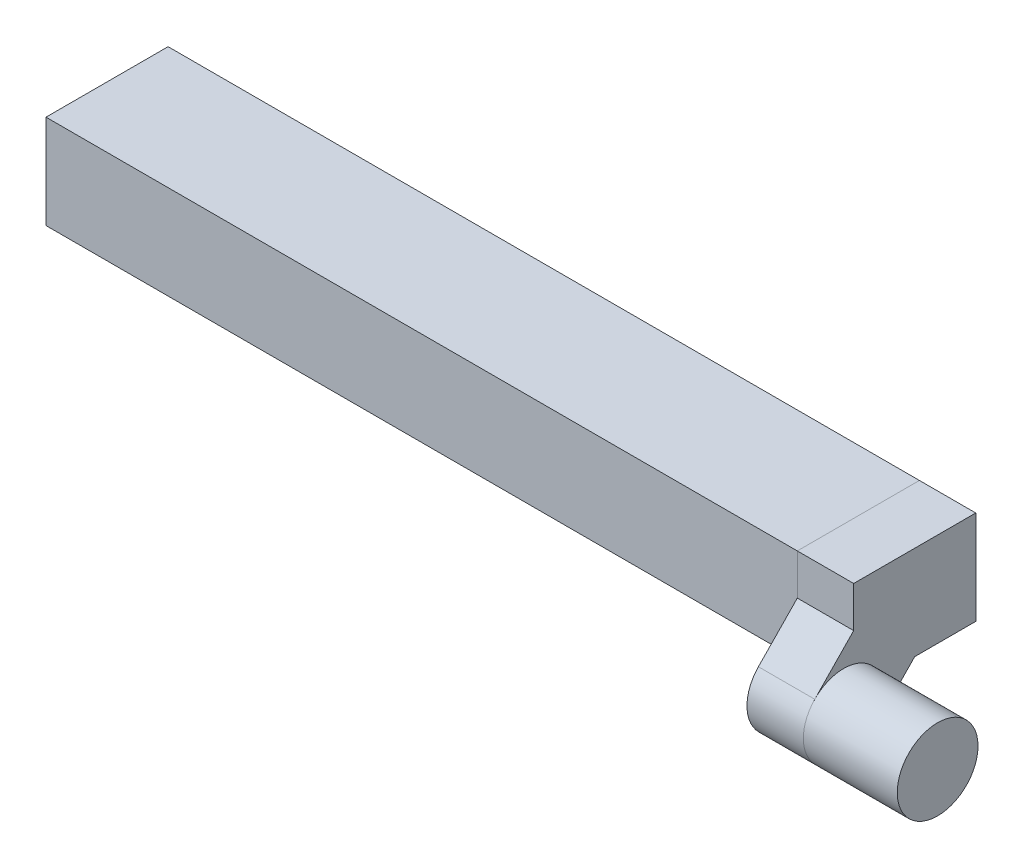
SolidWorks part; units mm, degrees
ref_plane "Front Plane" through (0, 0, 0) normal (0, 0, 1) x (1, 0, 0)
ref_plane "Top Plane" through (0, 0, 0) normal (0, 1, 0) x (1, 0, 0)
ref_plane "Right Plane" through (0, 0, 0) normal (1, 0, 0) x (0, 0, -1)
sketch "Sketch2" plane through (0, 0, 0) normal (1, 0, 0) x (0, 0, -1)
  line L1 (-2.05, -2.05) -> (2.05, -2.05)
  line L2 (-2.05, -2.05) -> (-2.05, 2.05)
  line L3 (-2.05, 2.05) -> (2.05, 2.05)
  line L4 (2.05, -2.05) -> (2.05, 2.05)
  line L5 (-2.05, -2.05) -> (2.05, 2.05) construction
  line L6 (-2.05, 2.05) -> (2.05, -2.05) construction
  line L7 (3.25, -2.5) -> (-3.25, -2.5)
  line L8 (3.25, -2.5) -> (3.25, 2.5)
  line L9 (3.25, 2.5) -> (-3.25, 2.5)
  line L10 (-3.25, -2.5) -> (-3.25, 2.5)
  line L11 (3.25, -2.5) -> (-3.25, 2.5) construction
  line L12 (3.25, 2.5) -> (-3.25, -2.5) construction
  point P0 (0, 0)
  point P5 (0, 0)
  dimension "D1" = 4.1
  dimension "D2" = 4.1
  dimension "D3" = 6.5
  dimension "D4" = 5
extrude "Boss-Extrude1" add sketch "Sketch2" along normal blind 10
extrude "Boss-Extrude2" add sketch "Sketch2<2>" along normal blind 25 from offset 15 contours L1 L4 L3 L2 | L10 L7 L8 L9 L4 L1 L2 L3 region at (0, 0, 0) region at (0, -2.418, 0)
sketch "Sketch2<2>" plane through (0, 0, 0) normal (1, 0, 0) x (0, 0, -1) same geometry as "Sketch2"
sketch "Sketch5" plane through (40, 0, 0) normal (1, 0, 0) x (0, 0, -1)
  line L0 (-0.02, -0.4959) -> (-4.75, -0.4959) construction
  line L6 (-3.25, 2.5) -> (3.25, 2.5)
  line L7 (3.25, 2.5) -> (3.25, -2.5)
  line L8 (3.25, -2.5) -> (0, -2.5)
  line L9 (-3.25, -2.5) -> (3.25, -2.5) construction
  line L10 (0, -2.5) -> (-2.2395, -4.8021)
  line L11 (-5.3217, -1.8038) -> (-3.25, 0.3258)
  line L12 (-3.25, -2.5) -> (-3.25, 2.5) construction
  line L13 (-5.3217, -1.8038) -> (-2.2395, -4.8021) construction
  line L14 (-3.25, 0.3258) -> (-3.25, 2.5)
  arc A1 (-5.3217, -1.8038) -> (-2.2395, -4.8021) centre (-3.7806, -3.303) ccw
  dimension "D1" = 4.73
  dimension "D3" = 5
  dimension "D4" = 4.3
extrude "Boss-Extrude3" add sketch "Sketch5" along normal blind 3
sketch "Sketch6" plane through (43, 0, 0) normal (1, 0, 0) x (0, 0, -1)
  circle A1 centre (-3.7806, -3.303) radius 2.15
  dimension "D1" = 4.3
extrude "Boss-Extrude4" add sketch "Sketch6" along normal blind 5
extrude "Boss-Extrude5" add sketch "Sketch2<4>" along normal blind 5 from offset 10
sketch "Sketch2<4>" plane through (0, 0, 0) normal (1, 0, 0) x (0, 0, -1) same geometry as "Sketch2"
